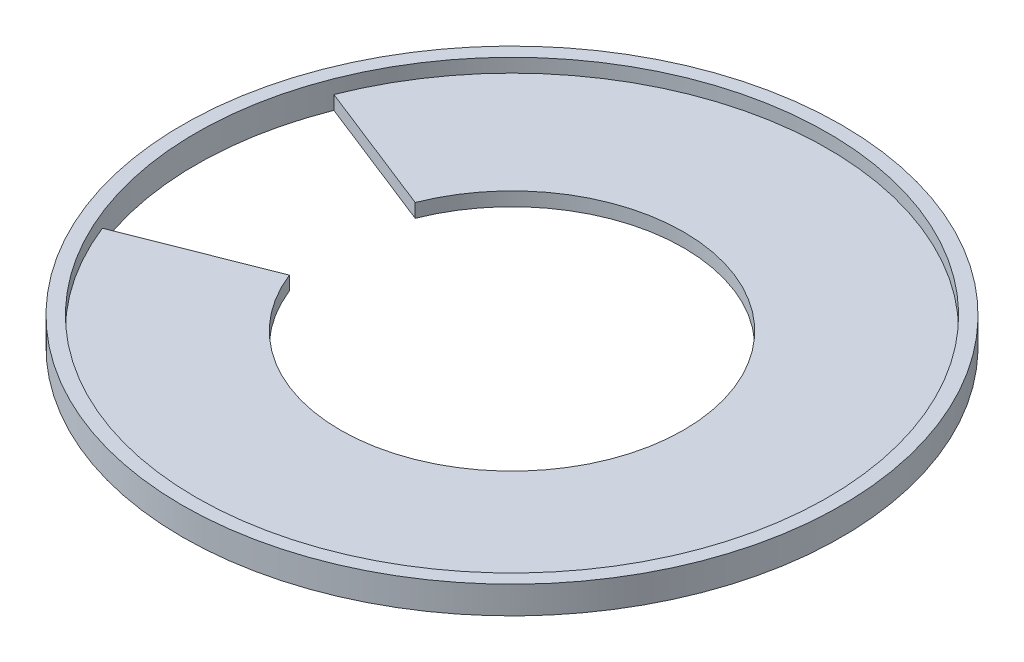
SolidWorks part; units mm, degrees
ref_plane "Front Plane" through (0, 0, 0) normal (0, 0, 1) x (1, 0, 0)
ref_plane "Top Plane" through (0, 0, 0) normal (0, 1, 0) x (1, 0, 0)
ref_plane "Right Plane" through (0, 0, 0) normal (1, 0, 0) x (0, 0, -1)
sketch "Sketch1" plane through (0, 0, 0) normal (0, 1, 0) x (1, 0, 0)
  line L0 (0, 0) -> (60.94, 0) construction
  line L1 (0, 0) -> (0, 51.613) construction
  line L2 (-23.2604, -9.1625) -> (-42.7992, -16.8591)
  line L3 (-23.2604, 9.1625) -> (-42.7992, 16.8591)
  circle A0 centre (0, 0) radius 25
  circle A1 centre (0, 0) radius 46
  circle A2 centre (0, 0) radius 48
  dimension "D1" = 50
  dimension "D2" = 92
  dimension "D3" = 2
  dimension "D4" = 21.5
  dimension "D5" = 21
extrude "Boss-Extrude1" add sketch "Sketch1" along normal blind 4 contours A2 A1 region at (-46.6424, 0, 0)
extrude "Boss-Extrude2" add sketch "Sketch1<3>" along normal blind 2 contours L2 A1 L3 A0 region at (4.9016, 0, 25.8175)
sketch "Sketch1<3>" plane through (0, 0, 0) normal (0, 1, 0) x (1, 0, 0) same geometry as "Sketch1"
